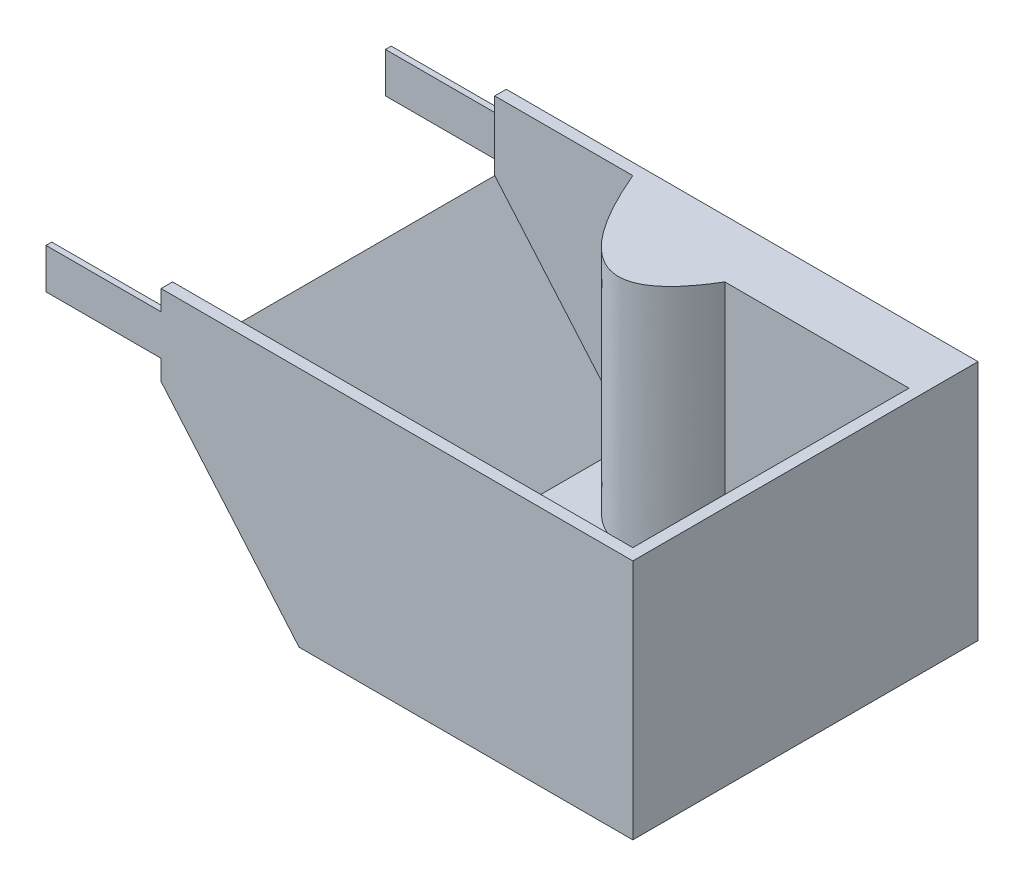
SolidWorks part; units mm, degrees
ref_plane "Alzado" through (0, 0, 0) normal (0, 0, 1) x (1, 0, 0)
ref_plane "Planta" through (0, 0, 0) normal (0, 1, 0) x (1, 0, 0)
ref_plane "Vista lateral" through (0, 0, 0) normal (1, 0, 0) x (0, 0, -1)
sketch "Croquis2" plane through (0, 0, 0) normal (0, 1, 0) x (1, 0, 0)
  line L0 (-200, 70) -> (200, 70)
  line L1 (-200, 70) -> (-200, -70)
  line L2 (-200, -70) -> (200, -70)
  line L3 (200, 70) -> (200, -70)
  line L4 (0, 70) -> (60, 70)
  line L5 (0, 70) -> (0, -70)
  line L6 (0, -70) -> (60, -70)
  line L7 (60, 70) -> (60, -70)
  line L8 (200, 70) -> (120, 70)
  line L9 (200, 70) -> (200, 50)
  line L10 (200, 50) -> (120, 50)
  line L11 (0, 70) -> (-60, 70)
  line L12 (0, 70) -> (0, 50)
  line L13 (0, 50) -> (-60, 50)
  line L14 (-60, 60.1561) -> (-60, 50)
  spline S0 degree 2 poles (60, 70) (89.7639, -0.5628) (120, 50) knots 0 0 0 1 1 1
  spline S1 degree 2 poles (-120, 70) (-89.7132, -0.7337) (-60, 50) knots 0 0 0 1 1 1
  point P14 (99.6856, 29.6804)
  point P15 (60, 70)
  point P16 (120, 50)
  point P18 (-120, 70)
  point P19 (-60, 50)
  point P20 (-79.8536, 29.6804)
extrude "Saliente-Extruir1" add sketch "Croquis2" along normal blind 105 contours L0 S0 L10 L3 region at (124.5586, 0, -56.2815)
extrude "Saliente-Extruir2" add sketch "Croquis2<3>" along normal blind 5 contours S0 L7 L2 L3 L10 region at (131.1472, 0, 11.8661)
sketch "Croquis2<3>" plane through (0, 0, 0) normal (0, 1, 0) x (1, 0, 0) same geometry as "Croquis2"
sketch "Croquis3" plane through (200, 0, 0) normal (1, 0, 0) x (0, 0, -1)
  line L1 (-70, 0) -> (70, 0)
  line L2 (-70, 0) -> (-70, 105)
  line L3 (-70, 105) -> (70, 105)
  line L4 (70, 0) -> (70, 105)
extrude "Saliente-Extruir3" add sketch "Croquis3" along normal blind 5
sketch "Croquis4" plane through (0, 0, 70) normal (0, 0, 1) x (1, 0, 0)
  line L0 (60, 0) -> (205, 0) construction
  line L5 (205, 105) -> (0, 105)
  line L6 (205, 105) -> (205, 0)
  line L7 (205, 0) -> (0, 0)
  line L8 (0, 105) -> (0, 0)
  dimension "D1" = 205
extrude "Saliente-Extruir5" add sketch "Croquis4" along normal blind 5
sketch "Croquis5" plane through (0, 0, -70) normal (0, 0, -1) x (-1, 0, 0)
  line L1 (-205, 0) -> (0, 0)
  line L2 (-205, 0) -> (-205, 105)
  line L3 (-205, 105) -> (0, 105)
  line L4 (0, 0) -> (0, 105)
  dimension "D1" = 205
extrude "Saliente-Extruir6" add sketch "Croquis5" along normal blind 5
sketch "Croquis6" plane through (0, 0, -70) normal (0, 0, 1) x (1, 0, 0)
  line L0 (0, 105) -> (0, 75) construction
  line L1 (0, 0) -> (0, 105) construction
  line L2 (60, 5) -> (0, 75)
  line L3 (60, 5) -> (60, 0)
  line L4 (0, 75) -> (0, 70)
  line L5 (60, 0) -> (0, 70)
  dimension "D1" = 30
  dimension "D2" = 5
extrude "Saliente-Extruir7" add sketch "Croquis6" along normal blind 140
sketch "Croquis8" plane through (0, 0, -70) normal (0, 0, 1) x (1, 0, 0)
  line L0 (60, 0) -> (0, 70)
  line L1 (60, 0) -> (0, 0)
  line L2 (0, 0) -> (0, 70)
extrude "Cortar-Extruir1" cut sketch "Croquis8" against normal through all both and the other way through all
sketch "Croquis9" plane through (0, 0, 75) normal (0, 0, 1) x (1, 0, 0)
  line L0 (0, 105) -> (0, 70) construction
  line L1 (0, 96.25) -> (20, 96.25)
  line L2 (0, 96.25) -> (0, 78.75)
  line L3 (0, 78.75) -> (20, 78.75)
  line L4 (20, 96.25) -> (20, 78.75)
  line L5 (205, 105) -> (0, 105) construction
  line L7 (0, 96.25) -> (-50, 96.25)
  line L8 (0, 96.25) -> (0, 78.75)
  line L9 (0, 78.75) -> (-50, 78.75)
  line L10 (-50, 96.25) -> (-50, 78.75)
  line M7 (0, 105) -> (0, 70)
  dimension "D1" = 20
  dimension "D2" = 17.5
  dimension "D3" = 8.75
  dimension "D4" = 50
extrude "Saliente-Extruir8" add sketch "Croquis9" against normal blind 2.5 contours L4 L1 L3 M7 | L7 L10 L9 M7 region at (10, 87.5, 75) region at (-25, 87.5, 75)
sketch "Croquis10" plane through (0, 0, -75) normal (0, 0, -1) x (-1, 0, 0)
  line L0 (0, 70) -> (0, 105) construction
  line L1 (0, 96.25) -> (-20, 96.25)
  line L2 (0, 96.25) -> (0, 78.75)
  line L3 (0, 78.75) -> (-20, 78.75)
  line L4 (-20, 96.25) -> (-20, 78.75)
  line L5 (0, 105) -> (-205, 105) construction
  line L7 (0, 96.25) -> (50, 96.25)
  line L8 (0, 96.25) -> (0, 78.75)
  line L9 (0, 78.75) -> (50, 78.75)
  line L10 (50, 96.25) -> (50, 78.75)
  line M6 (0, 70) -> (0, 105)
  dimension "D1" = 20
  dimension "D2" = 17.5
  dimension "D3" = 8.75
  dimension "D4" = 50
extrude "Saliente-Extruir9" add sketch "Croquis10" against normal blind 2.5 contours L1 L4 L3 M6 | L10 L7 L9 M6 region at (10, 87.5, -75) region at (-25, 87.5, -75)
sketch "Croquis11" plane through (0, 105, 0) normal (0, 1, 0) x (1, 0, 0)
  line L6 (65.5711, 70) -> (195, 70)
  line L7 (195, 55) -> (195, 70)
  line L8 (117.1633, 55) -> (195, 55)
  parabola Q0 (60, 70) -> (120, 50) focus (94.8097, 36.3425) apex (94.7807, 28.8931) construction
  parabola Q1 (60, 70) -> (120, 50) focus (94.8097, 36.3425) apex (94.7807, 28.8931) construction
  spline S4 degree 2 poles (117.1633, 55) (116.5535, 53.9811) (115.344, 51.9514) (113.6241, 49.1815) (110.1898, 44.2105) (105.0569, 38.4547) (100.4235, 35.2649) (97.5017, 34.1855) (95.328, 33.847) (93.1935, 33.9721) (90.3912, 34.735) (85.948, 37.3662) (78.79, 44.7361) (74.1645, 52.5134) knots -0.028794 -0.028794 -0.028794 -0.004728 0.019338 0.06747 0.163734 0.292085 0.388349 0.452525 0.5167 0.580876 0.67714 0.805491 0.998019 0.998019 0.998019
  spline S5 degree 1 poles (74.1645, 52.5134) (65.5711, 70) knots 0.003087 0.003087 0.319062 0.319062
  point P6 (94.7807, 28.8931)
extrude "Cortar-Extruir2" cut sketch "Croquis11" against normal blind 140 from offset 5 contours L6 L7 L8 S4 S5 offset against normal yes
